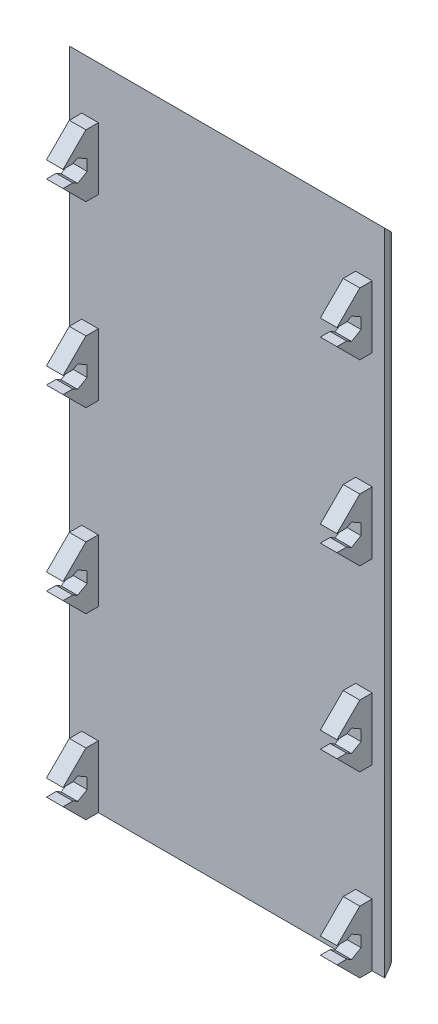
SolidWorks part; units mm, degrees
ref_plane "Front Plane" through (0, 0, 0) normal (0, 0, 1) x (1, 0, 0)
ref_plane "Top Plane" through (0, 0, 0) normal (0, 1, 0) x (1, 0, 0)
ref_plane "Right Plane" through (0, 0, 0) normal (1, 0, 0) x (0, 0, -1)
sketch "Sketch1" plane through (0, 0, 0) normal (0, 1, 0) x (1, 0, 0)
  line L0 (-9.2151, 0) -> (-9.2151, -10)
  line L1 (-9.2151, -10) -> (-5.2151, -10)
  line L2 (-5.2151, -10) -> (-5.2151, 0)
  line L3 (-5.2151, 0) -> (56.7849, 0)
  line L4 (56.7849, 0) -> (56.7849, -10)
  line L5 (56.7849, -10) -> (60.7849, -10)
  line L6 (60.7849, -10) -> (60.7849, 0)
  line L7 (60.7849, 0) -> (63.7849, 0)
  line L8 (-9.2151, 0) -> (-12.2151, 0)
  line L9 (-12.2151, 0) -> (-8.1737, 7)
  line L10 (-8.1737, 7) -> (59.7434, 7)
  line L11 (59.7434, 7) -> (63.7849, 0)
  line L12 (25.7849, 7) -> (25.7849, 0) construction
  dimension "D1" = 3
  dimension "D2" = 10
  dimension "D3" = 70
  dimension "D4" = 7
  dimension "D5" = 4
  dimension "D6" = 60
extrude "Boss-Extrude1" add sketch "Sketch1" along normal blind 156.5
sketch "Sketch4" plane through (60.7849, 0, 0) normal (1, 0, 0) x (0, 0, -1)
  line L0 (0, 156.5) -> (0, 0) construction
  line L1 (-37.5185, 156.5) -> (0, 156.5)
  line L2 (-37.5185, 156.5) -> (-37.5185, 144)
  line L3 (-37.5185, 144) -> (0, 144)
  line L4 (0, 156.5) -> (0, 144)
  line L5 (-37.5185, 156.5) -> (0, 144) construction
  line L6 (-37.5185, 144) -> (0, 156.5) construction
  line L7 (-10, 156.5) -> (0, 156.5) construction
  point P0 (-18.7592, 150.25)
  dimension "D1" = 12.5
extrude "Cut-Extrude1" cut sketch "Sketch4" against normal through all
sketch "Sketch5" plane through (60.7849, 0, 0) normal (1, 0, 0) x (0, 0, -1)
  line L0 (0, 156.5) -> (0, 0) construction
  line L1 (-33.3149, 129) -> (0, 129)
  line L2 (-33.3149, 129) -> (-33.3149, 101)
  line L3 (-33.3149, 101) -> (0, 101)
  line L4 (0, 129) -> (0, 101)
  line L5 (-33.3149, 129) -> (0, 101) construction
  line L6 (-33.3149, 101) -> (0, 129) construction
  line L7 (-10, 144) -> (0, 144) construction
  point P0 (-16.6574, 115)
  dimension "D1" = 28
  dimension "D2" = 15
extrude "Cut-Extrude2" cut sketch "Sketch5" against normal through all
sketch "Sketch6" plane through (0, 0, 0) normal (1, 0, 0) x (0, 0, -1)
  line L0 (-10, 144) -> (-10, 129) construction
  line L1 (-2.7, 137.8279) -> (-5, 139.1558)
  line L2 (-5, 139.1558) -> (-7.3, 137.8279)
  line L3 (-7.3, 137.8279) -> (-7.3, 135.1721)
  line L4 (-7.3, 135.1721) -> (-5, 133.8442)
  line L5 (-5, 133.8442) -> (-2.7, 135.1721)
  line L6 (-2.7, 135.1721) -> (-2.7, 137.8279)
  line L7 (-10, 144) -> (0, 144) construction
  line L8 (-6.15, 138.4919) -> (-10, 138.4919)
  line L9 (-6.15, 134.5081) -> (-10, 134.5081)
  line L10 (-10, 134.5081) -> (-10, 138.4919)
  circle A1 centre (-5, 136.5) radius 2.3 construction
  dimension "D1" = 4.6
  dimension "D2" = 7.5
  dimension "D3" = 5
extrude "Cut-Extrude3" cut sketch "Sketch6" against normal through all and the other way through all contours L10 L9 L4 L3 L2 L8 | L5 L6 L1 L2 L3 L4 region at (0, 136.5, 5) region at (0, 136.5, 8.5351)
pattern_linear "LPattern1" count 4 spacing 43 along (0, -1, 0) of "Cut-Extrude2", "Cut-Extrude3"
chamfer "Chamfer3" distance 7 angle 45 1 edges at (25.7849, 156.5, -7)
fillet "Fillet1" radius 8 2 edges at (-8.1737, 74.75, -7) (59.7434, 74.75, -7)
chamfer "Chamfer5" distance 7 angle 45 16 edges at (58.7849, 43, 10) (58.7849, 144, 10) (58.7849, 129, 10) (-7.2151, 144, 10) (-7.2151, 129, 10) (-7.2151, 101, 10) (-7.2151, 86, 10) (58.7849, 101, 10) (58.7849, 86, 10) (58.7849, 58, 10) (58.7849, 0, 10) (58.7849, 15, 10) (-7.2151, 0, 10) (-7.2151, 15, 10) (-7.2151, 58, 10) (-7.2151, 43, 10)
sketch "Sketch7" plane through (0, 0, -7) normal (0, 0, -1) x (-1, 0, 0)
  line L0 (-11.7849, 94.4158) -> (-39.7849, 94.4158) construction
  line L1 (-11.7849, 94.4158) -> (-11.7849, 55.0842) construction
  line L2 (-39.7849, 94.4158) -> (-39.7849, 55.0842) construction
  line L3 (-11.7849, 55.0842) -> (-39.7849, 55.0842) construction
  line L4 (-11.7849, 94.4158) -> (-11.7849, 87.9932)
  line L5 (-11.7849, 94.4158) -> (-39.7849, 94.4158)
  line L6 (-11.7849, 87.4158) -> (-39.7849, 87.4158) construction
  line L7 (-39.7849, 94.4158) -> (-39.7849, 87.9932)
  line L8 (3.5549, 55.0842) -> (-11.7849, 55.0842) construction
  line L9 (-11.7849, 79.3329) -> (-18.2849, 75.5801)
  line L10 (-12.2849, 87.1271) -> (-25.7849, 79.3329)
  line L11 (-25.7849, 79.3329) -> (-39.2849, 87.1271)
  line L14 (-25.7849, 71.25) -> (-39.2849, 63.4558)
  line L15 (-11.7849, 79.3329) -> (-11.7849, 65.5842)
  line L16 (-39.7849, 62.5897) -> (-39.7849, 55.0842)
  line L17 (-39.7849, 55.0842) -> (-32.7849, 59.1256)
  line L18 (-32.7849, 59.1256) -> (-32.7849, 65.5842)
  line L19 (-18.7849, 74.7141) -> (-18.7849, 65.5842)
  line L20 (-11.7849, 65.5842) -> (-32.7849, 65.5842) construction
  line L21 (-25.7849, 71.25) -> (-25.7849, 65.5842)
  line L22 (-18.7849, 65.5842) -> (-25.7849, 65.5842) construction
  line L23 (-32.7849, 83.3744) -> (-39.2849, 79.6216)
  line L24 (3.5549, 0) -> (3.5549, 149.5) construction
  line L25 (-39.7849, 78.7556) -> (-39.7849, 71.8274)
  line L26 (-25.7849, 79.3329) -> (-32.7849, 75.2915)
  line L27 (-32.7849, 75.2915) -> (-25.7849, 71.25)
  line L28 (-11.7849, 55.0842) -> (-39.7849, 55.0842) construction
  line L29 (-39.7849, 55.0842) -> (-55.1246, 55.0842) construction
  line L30 (-55.1246, 149.5) -> (-55.1246, 0) construction
  line L31 (-11.7849, 149.5) -> (-11.7849, 94.4158) construction
  line L32 (3.5549, 149.5) -> (-55.1246, 149.5) construction
  line L33 (-11.7849, 55.0842) -> (-11.7849, 0) construction
  line L34 (-55.1246, 0) -> (3.5549, 0) construction
  line L35 (-39.2849, 70.9613) -> (-32.7849, 67.2085)
  line L38 (-32.7849, 59.1256) -> (-31.2016, 60.0397)
  arc A0 (-11.7849, 65.5842) -> (-32.7849, 65.5842) centre (-22.2849, 65.5842) cw
  arc A1 (-18.7849, 65.5842) -> (-25.7849, 65.5842) centre (-22.2849, 65.5842) cw
  arc A3 (-18.2849, 75.5801) -> (-18.7849, 74.7141) centre (-17.7849, 74.7141) ccw
  arc A4 (-11.7849, 87.9932) -> (-12.2849, 87.1271) centre (-12.7849, 87.9932) cw
  arc A5 (-39.2849, 87.1271) -> (-39.7849, 87.9932) centre (-38.7849, 87.9932) cw
  arc A7 (-39.7849, 71.8274) -> (-39.2849, 70.9613) centre (-38.7849, 71.8274) ccw
  arc A8 (-39.2849, 79.6216) -> (-39.7849, 78.7556) centre (-38.7849, 78.7556) ccw
  arc A9 (-39.2849, 63.4558) -> (-39.7849, 62.5897) centre (-38.7849, 62.5897) ccw
  point P43 (-39.7849, 63.1671)
  point P50 (-39.7849, 63.1671)
  point P52 (-39.7849, 63.1671)
  point P57 (-39.7849, 71.25)
  point P60 (-39.7849, 79.3329)
  dimension "D11" = 7
  dimension "D12" = 7
  dimension "D10" = 7
  dimension "D14" = 1
  dimension "D16" = 1
  dimension "D6" = 1
  dimension "D13" = 1
  dimension "D2" = 7
  dimension "D3" = 7
  dimension "D4" = 30
  dimension "D5" = 30
  dimension "D7" = 7
  dimension "D8" = 7
  dimension "D9" = 7
  dimension "D15" = 30
extrude "Cut-Extrude4" cut sketch "Sketch7" against normal blind 1 contours L5 L7 L6 L4 | L6 L11 L10 | L27 L26 L11 L9 | L19 A1 L21 L9 L16 L17 L18 A0 L15 | L38 A0 L18 region at (25.7849, 88.6489, -7) region at (33.7137, 75.2915, -7) region at (26.1553, 68.4171, -7) region at (32.3046, 61.0644, -7)
fillet "Fillet2" radius 1 3 edges at (25.7849, 71.25, -6.5) (39.7849, 94.4158, -6.5) (11.7849, 94.4158, -6.5)
